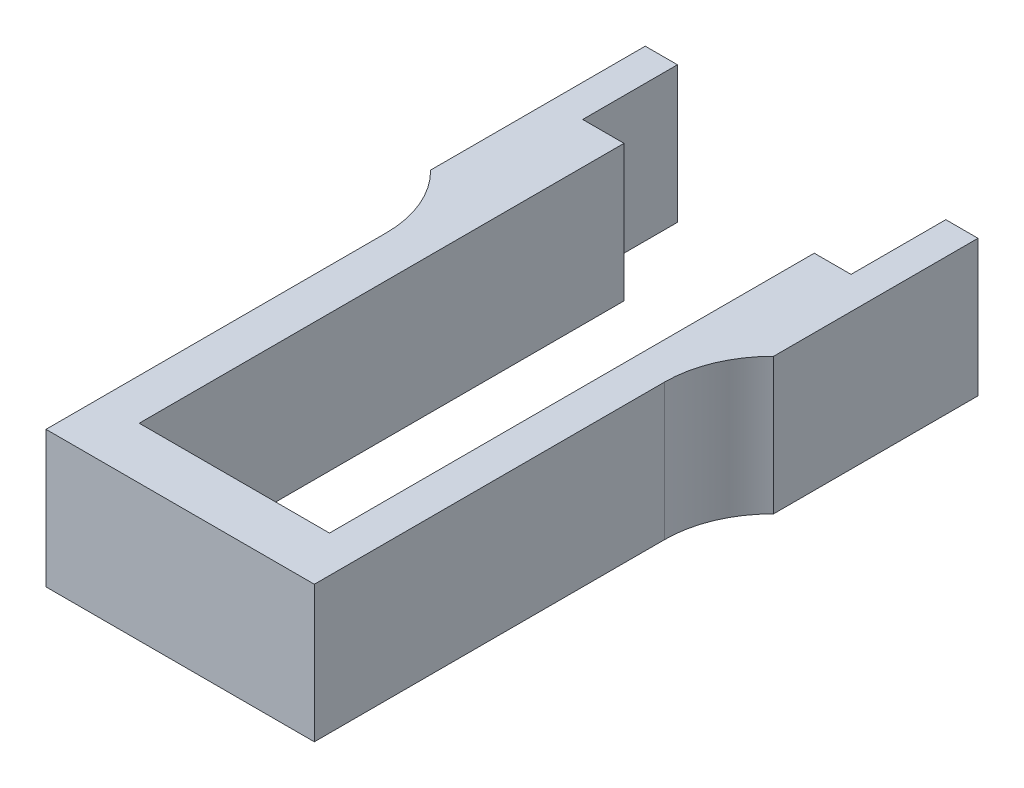
SolidWorks part; units mm, degrees
ref_plane "Ön Düzlem" through (0, 0, 0) normal (0, 0, 1) x (1, 0, 0)
ref_plane "Üst Düzlem" through (0, 0, 0) normal (0, 1, 0) x (1, 0, 0)
ref_plane "Sağ Düzlem" through (0, 0, 0) normal (1, 0, 0) x (0, 0, -1)
sketch "Sketch1" plane through (0, 0, 0) normal (0, 0, 1) x (1, 0, 0)
  line L0 (-25, 3) -> (-25, 97) construction
  line L1 (-21.15, 85.506) -> (-25, 85.506)
  line L2 (-21.15, 85.506) -> (-21.15, 72.7911)
  line L3 (-21.15, 72.7911) -> (-25, 72.7911)
  line L4 (-25, 85.506) -> (-25, 72.7911)
  dimension "D1" = 3.85
extrude "Boss-Extrude1" add sketch "Sketch1" along normal blind 50
sketch "Sketch3" plane through (0, 85.506, 0) normal (0, 1, 0) x (1, 0, 0)
  line L0 (-21.15, -50) -> (-21.15, 0) construction
  line L1 (-21.15, -45.1655) -> (-3.424, -45.1655)
  line L2 (-21.15, -45.1655) -> (-21.15, -50)
  line L3 (-21.15, -50) -> (0, -50)
  line L5 (-21.15, -50) -> (-25, -50) construction
  line L6 (-3.424, -45.1655) -> (-3.424, 0)
  line L7 (-22, 0) -> (-3, 0) construction
  line L8 (-3.424, 0) -> (0, 0)
  line L9 (0, 0) -> (0, -50)
extrude "Boss-Extrude2" add sketch "Sketch3" against normal up to surface (12.7149 mm away) up to face at (-23.075, 72.7911, 25)
sketch "Sketch4" plane through (0, 0, 0) normal (1, 0, 0) x (0, 0, -1)
  line L0 (-50, 85.506) -> (0, 85.506) construction
  line L1 (-10.2237, 85.506) -> (8.8288, 85.506)
  line L2 (-10.2237, 85.506) -> (-10.2237, 72.7911)
  line L3 (-10.2237, 72.7911) -> (8.8288, 72.7911)
  line L4 (8.8288, 85.506) -> (8.8288, 72.7911)
  line L5 (0, 72.7911) -> (-50, 72.7911) construction
extrude "Boss-Extrude3" add sketch "Sketch4" along normal blind 3
fillet "Fillet1" radius 10 1 edges at (0, 79.1485, 10.2237)
ref_plane "Plane1" through (-12.5, 0, 0) normal (-1, 0, 0) x (0, 0, 1)
sketch "Sketch5" plane through (-25, 0, 0) normal (-1, 0, 0) x (0, 0, 1)
  line L0 (50, 85.506) -> (0, 85.506) construction
  line L1 (11.1704, 85.506) -> (-8.8288, 85.506)
  line L2 (11.1704, 85.506) -> (11.1704, 72.7911)
  line L3 (11.1704, 72.7911) -> (-8.8288, 72.7911)
  line L4 (-8.8288, 85.506) -> (-8.8288, 72.7911)
  line L5 (0, 72.7911) -> (-8.8288, 72.7911) construction
  line L6 (-8.8288, 72.7911) -> (-8.8288, 85.506) construction
extrude "Boss-Extrude4" add sketch "Sketch5" along normal blind 3
fillet "Fillet2" radius 10 1 edges at (-25, 79.1485, 11.1704)
